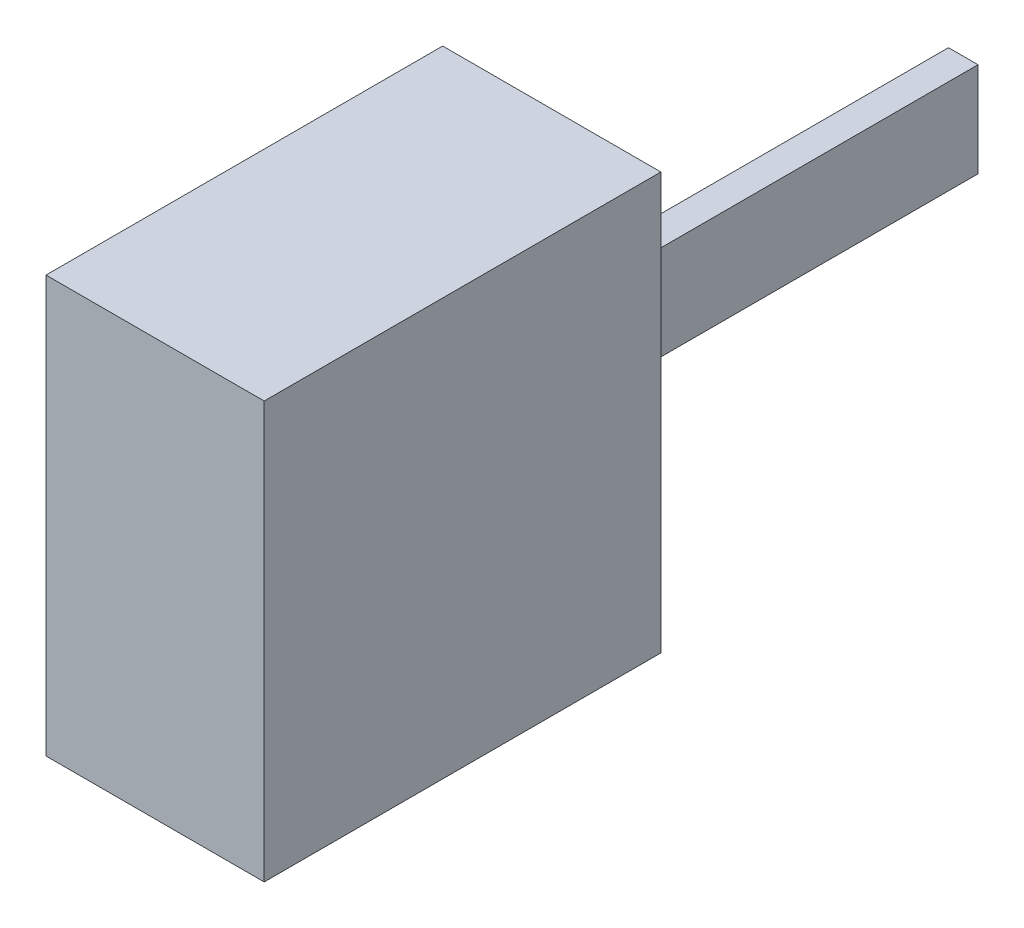
SolidWorks part; units mm, degrees
ref_plane "Front Plane" through (0, 0, 0) normal (0, 0, 1) x (1, 0, 0)
ref_plane "Top Plane" through (0, 0, 0) normal (0, 1, 0) x (1, 0, 0)
ref_plane "Right Plane" through (0, 0, 0) normal (1, 0, 0) x (0, 0, -1)
sketch "Sketch1" plane through (0, 0, 0) normal (0, 0, 1) x (1, 0, 0)
  line L1 (-16.5, 25.875) -> (16.5, 25.875)
  line L2 (-16.5, 25.875) -> (-16.5, -37.125)
  line L3 (-16.5, -37.125) -> (16.5, -37.125)
  line L4 (16.5, 25.875) -> (16.5, -37.125)
  line L5 (4.4667, -10.385) -> (0, -10.385)
  line L6 (4.4667, -10.385) -> (4.4667, 3.9088)
  line L7 (4.4667, 3.9088) -> (0, 3.9088)
  line L8 (0, -10.385) -> (0, 3.9088)
  dimension "D1" = 63
  dimension "D2" = 33
  dimension "D3" = 16.5
extrude "Boss-Extrude1" add sketch "Sketch1" along normal blind 60 contours L8 L5 L6 L7 | L4 L1 L2 L3 L5 L8 L7 L6 region at (-0.0708, -5.7006, 0) region at (2.2334, -3.2381, 0)
extrude "Boss-Extrude2" add sketch "Sketch1<3>" against normal blind 60 contours L8 L5 L6 L7 region at (2.2334, -3.2381, 0)
sketch "Sketch1<3>" plane through (0, 0, 0) normal (0, 0, 1) x (1, 0, 0) same geometry as "Sketch1"
